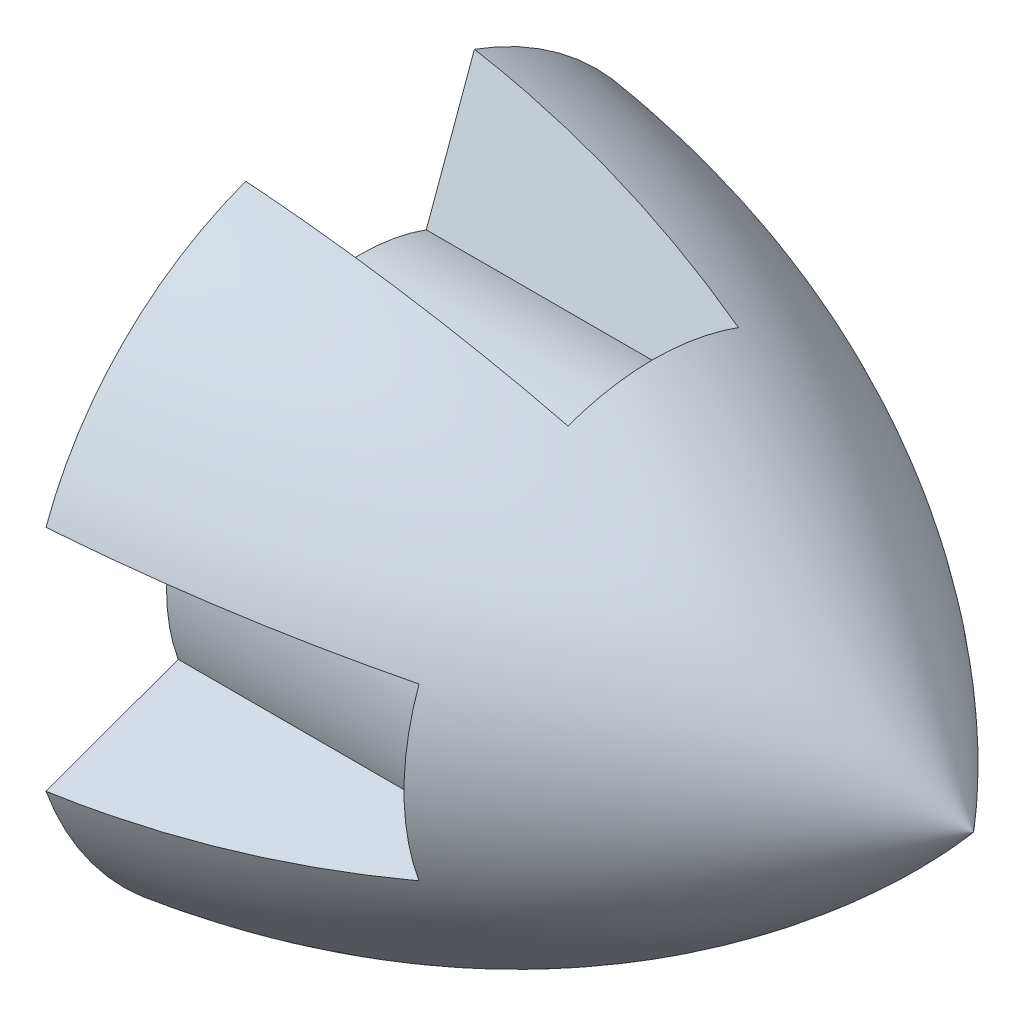
SolidWorks part; units mm, degrees
ref_plane "Спереди" through (0, 0, 0) normal (0, 0, 1) x (1, 0, 0)
ref_plane "Сверху" through (0, 0, 0) normal (0, 1, 0) x (1, 0, 0)
ref_plane "Справа" through (0, 0, 0) normal (1, 0, 0) x (0, 0, -1)
sketch "Эскиз2" plane through (0, 0, 0) normal (0, 0, 1) x (1, 0, 0)
  line L0 (0, 0) -> (0, 28.5)
  line L1 (0, 0) -> (28.5, 0)
  line L2 (-1000, 0) -> (49000, 0) construction
  line L3 (28.5, 0) -> (52.3107, 0)
  spline S0 degree 2 poles (0, 28.5) (31.309, 24.448) (52.3107, 0) knots 0 0 0 1 1 1
revolve "Повернуть1" add sketch "Эскиз2" angle 360 about L2
sketch "Эскиз7" plane through (0, 0, 0) normal (-1, 0, 0) x (0, 0, 1)
  circle A0 centre (0, 0) radius 12.6
extrude "Вырез-Вытянуть1" cut sketch "Эскиз7" against normal blind 15
sketch "Эскиз8" plane through (0, 0, 0) normal (-1, 0, 0) x (0, 0, 1)
  circle A0 centre (0, 0) radius 16.5
extrude "Вырез-Вытянуть2" cut sketch "Эскиз8" against normal blind 1
sketch "Эскиз11" plane through (0, 0, 0) normal (-1, 0, 0) x (0, 0, 1)
  line L0 (0, 0) -> (17101.0072, 46984.631) construction
  line L1 (0, 0) -> (-17101.0072, 46984.631) construction
  line L2 (-9.7476, 26.7812) -> (-5.6433, 15.5049)
  line L3 (9.7476, 26.7812) -> (5.6433, 15.5049)
  arc A0 (-5.6433, 15.5049) -> (5.6433, 15.5049) centre (0, 0) cw
  circle A1 centre (0, 0) radius 16.5 construction
  arc A2 (-9.7476, 26.7812) -> (9.7476, 26.7812) centre (0, 0) cw
  circle A3 centre (0, 0) radius 28.5 construction
extrude "Вырез-Вытянуть3" cut sketch "Эскиз11" against normal blind 25
pattern_circular "Круговой массив1" count 4 over 360 about axis through (1, 0, 0) along (-1, 0, 0) of "Вырез-Вытянуть3"
sketch "Эскиз12" plane through (1, 0, 0) normal (-1, 0, 0) x (0, 0, 1)
  circle A0 centre (0, 0) radius 12.6
  circle A1 centre (0, 0) radius 16.5
extrude "Бобышка-Вытянуть1" add sketch "Эскиз12" along normal blind 1
